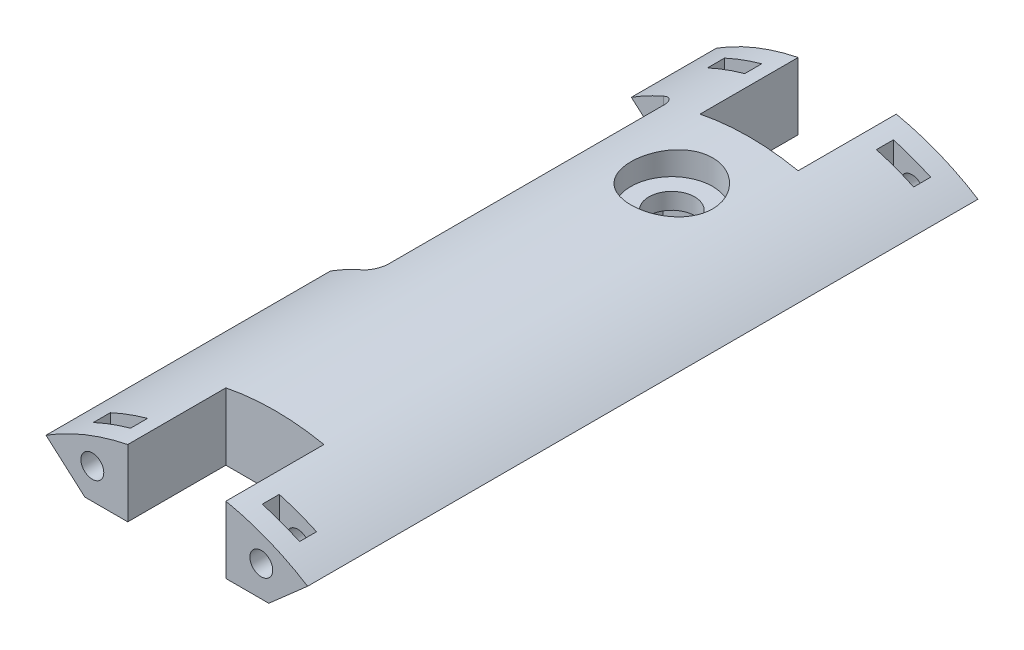
SolidWorks part; units mm, degrees
ref_plane "Plan de face" through (0, 0, 0) normal (0, 0, 1) x (1, 0, 0)
ref_plane "Plan de dessus" through (0, 0, 0) normal (0, 1, 0) x (1, 0, 0)
ref_plane "Plan de droite" through (0, 0, 0) normal (1, 0, 0) x (0, 0, -1)
sketch "Esquisse3" plane through (0, 0, 0) normal (0, 0, 1) x (1, 0, 0)
  line L0 (-14.0624, 26.5) -> (-20, 31.7214)
  line L1 (14.0624, 26.5) -> (20, 31.7214)
  line L2 (-14.0624, 26.5) -> (14.0624, 26.5)
  line L3 (-20, 31.7214) -> (20, 31.7214) construction
  line L4 (-20, 31.7214) -> (-20, 0) construction
  line L5 (-20, 0) -> (20, 0) construction
  line L6 (20, 31.7214) -> (20, 0) construction
  line L7 (8.9994, 41.4168) -> (9.1038, 41.3823)
  circle A0 centre (0, 0) radius 37.5 construction
  circle A1 centre (0, 0) radius 30 construction
  arc A2 (-20, 31.7214) -> (20, 31.7214) centre (0, 0) cw
  point P5 (0, 0)
  point P15 (0, 26.5)
  dimension "D1" = 75
  dimension "D2" = 60
  dimension "D4" = 26.5
  dimension "D3" = 40
extrude "Boss.-Extru.2" add sketch "Esquisse3" along normal blind 102.5 contours A2 L0 L2 L1 region at (0, 31.5038, 0)
sketch "Esquisse7" plane through (0, 0, 102.5) normal (0, 0, 1) x (1, 0, 0)
  line L0 (0, 33.75) -> (0, 0) construction
  line L1 (0, 0) -> (-12.9156, 31.1809) construction
  line L2 (0, 0) -> (12.9156, 31.1809) construction
  line L3 (-30, 0) -> (-37.5, 0) construction
  circle A0 centre (0, 0) radius 33.75 construction
  circle A2 centre (-12.9156, 31.1809) radius 1.75
  circle A3 centre (12.9156, 31.1809) radius 1.75
  circle A4 centre (0, 0) radius 37.5 construction
  circle A5 centre (0, 0) radius 30 construction
  arc A6 (20, 31.7214) -> (-20, 31.7214) centre (0, 0) ccw construction
  point P15 (-33.75, 0)
  dimension "D2" = 3.5
  dimension "D5" = 60
  dimension "D3" = 22.5
  dimension "D4" = 22.5
extrude "Enlèv. mat.-Extru.4" cut sketch "Esquisse7" against normal blind 12
sketch "Esquisse11" plane through (0, 0, 102.5) normal (0, 0, 1) x (1, 0, 0)
  line L0 (-12.9156, 31.1809) -> (-15.7656, 31.1809) construction
  line L1 (-15.7656, 31.1809) -> (-15.7656, 34.0249)
  line L2 (-15.7656, 31.1809) -> (-15.7656, 29.4264)
  line L3 (-15.7656, 29.4264) -> (-12.9156, 27.7809)
  line L4 (-12.9156, 27.7809) -> (-10.0656, 29.4264)
  line L5 (-10.0656, 29.4264) -> (-10.0656, 36.1239)
  line L6 (10.0656, 36.1239) -> (10.0656, 29.4264)
  line L7 (10.0656, 29.4264) -> (12.9156, 27.7809)
  line L8 (12.9156, 27.7809) -> (15.7656, 29.4264)
  line L9 (15.7656, 29.4264) -> (15.7656, 34.0249)
  line L10 (12.9156, 31.1809) -> (15.7656, 31.1809) construction
  line L11 (12.9156, 31.1809) -> (10.0656, 31.1809) construction
  line L12 (12.9156, 31.1809) -> (12.9156, 27.7809) construction
  line L13 (11.1341, 33.0694) -> (11.2201, 33.0694) construction
  arc A1 (20, 31.7214) -> (-20, 31.7214) centre (0, 0) ccw construction
  arc A2 (-15.7656, 34.0249) -> (-10.0656, 36.1239) centre (0, 0) cw
  arc A3 (10.0656, 36.1239) -> (15.7656, 34.0249) centre (0, 0) cw
  dimension "D1" = 5.7
  dimension "D2" = 120
  dimension "D3" = 3.4
  dimension "D4" = 5.7
  dimension "D5" = 3.4
  dimension "D6" = 120
extrude "Enlèv. mat.-Extru.5" cut sketch "Esquisse11" against normal blind 2.6 from offset 3 offset against normal yes
sketch "Esquisse12" plane through (0, 0, 0) normal (0, 0, -1) x (-1, 0, 0)
  line L0 (0, 0) -> (0, 33.75) construction
  line L1 (0, 0) -> (-12.9156, 31.1809) construction
  line L2 (0, 0) -> (12.9156, 31.1809) construction
  line L3 (-30, 0) -> (-37.5, 0) construction
  circle A0 centre (0, 0) radius 33.75 construction
  circle A1 centre (-12.9156, 31.1809) radius 1.75
  circle A2 centre (12.9156, 31.1809) radius 1.75
  circle A3 centre (0, 0) radius 30 construction
  circle A4 centre (0, 0) radius 37.5 construction
  arc A5 (20, 31.7214) -> (-20, 31.7214) centre (0, 0) ccw construction
  point P15 (-33.75, 0)
  dimension "D4" = 3.5
  dimension "D5" = 60
  dimension "D1" = 22.5
  dimension "D2" = 22.5
extrude "Enlèv. mat.-Extru.6" cut sketch "Esquisse12" against normal blind 12
sketch "Esquisse14" plane through (0, 0, 0) normal (0, 0, -1) x (-1, 0, 0)
  line L0 (-12.9156, 31.1809) -> (-15.7656, 31.1809) construction
  line L1 (-15.7656, 31.1809) -> (-15.7656, 34.0249)
  line L2 (-15.7656, 31.1809) -> (-15.7656, 29.4264)
  line L3 (-15.7656, 29.4264) -> (-12.9156, 27.7809)
  line L4 (-12.9156, 27.7809) -> (-10.0656, 29.4264)
  line L5 (-10.0656, 29.4264) -> (-10.0656, 36.1239)
  line L6 (10.0656, 36.1239) -> (10.0656, 29.4264)
  line L7 (10.0656, 29.4264) -> (12.9156, 27.7809)
  line L8 (12.9156, 27.7809) -> (15.7656, 29.4264)
  line L9 (15.7656, 29.4264) -> (15.7656, 34.0249)
  line L10 (11.1656, 31.1809) -> (14.6656, 31.1809) construction
  line L11 (-14.6656, 31.1809) -> (-11.1656, 31.1809) construction
  line L12 (-12.9156, 32.9309) -> (-12.9156, 29.4309) construction
  line L13 (12.9156, 32.9309) -> (12.9156, 29.4309) construction
  line L14 (12.9156, 31.1809) -> (10.0656, 31.1809) construction
  line L15 (12.9156, 31.1809) -> (15.7656, 31.1809) construction
  circle A1 centre (-12.9156, 31.1809) radius 1.75 construction
  arc A2 (-15.7656, 34.0249) -> (-10.0656, 36.1239) centre (0, 0) cw
  arc A3 (10.0656, 36.1239) -> (15.7656, 34.0249) centre (0, 0) cw
  arc A4 (20, 31.7214) -> (-20, 31.7214) centre (0, 0) ccw construction
  circle A5 centre (-12.9156, 31.1809) radius 1.75 construction
  circle A6 centre (12.9156, 31.1809) radius 1.75 construction
  circle A7 centre (12.9156, 31.1809) radius 1.75 construction
  point P31 (-12.9156, 31.1809)
  point P36 (12.9156, 31.1809)
  dimension "D1" = 5.7
  dimension "D6" = 3.4
  dimension "D2" = 120
  dimension "D3" = 3.4
  dimension "D4" = 5.7
  dimension "D5" = 120
extrude "Enlèv. mat.-Extru.7" cut sketch "Esquisse14" against normal blind 2.6 from offset 3 offset against normal yes
sketch "Esquisse18" plane through (0, 0, 0) normal (0, 0, -1) x (-1, 0, 0)
  line L0 (14.0624, 26.5) -> (-14.0624, 26.5) construction
  line L1 (-7.15, 26.5) -> (7.15, 26.5)
  line L2 (-7.15, 26.5) -> (-7.15, 31.2)
  line L3 (-7.15, 31.2) -> (7.15, 31.2)
  line L4 (7.15, 26.5) -> (7.15, 31.2)
  point P6 (0, 31.2)
  dimension "D1" = 31.2
  dimension "D2" = 14.3
extrude "Enlèv. mat.-Extru.11" cut sketch "Esquisse18" against normal blind 11.74 from offset 21 offset against normal yes
sketch "Esquisse19" plane through (0, 31.2, 0) normal (0, -1, 0) x (-1, 0, 0)
  circle A0 centre (0, -26.82) radius 3.5
  dimension "D1" = 7
extrude "Enlèv. mat.-Extru.12" cut sketch "Esquisse19" against normal through all
sketch "Esquisse20" plane through (0, 31.2, 0) normal (0, -1, 0) x (-1, 0, 0)
  circle A0 centre (0, -26.82) radius 6.25
  dimension "D1" = 12.5
extrude "Enlèv. mat.-Extru.13" cut sketch "Esquisse20" against normal through all from offset 2.5 offset against normal yes
sketch "Esquisse21" plane through (0, 26.5, 0) normal (0, -1, 0) x (1, 0, 0)
  line L0 (-14.0624, 102.5) -> (14.0624, 102.5) construction
  line L1 (-7.5, 102.5) -> (7.5, 102.5)
  line L2 (-7.5, 102.5) -> (-7.5, 87.5)
  line L3 (-7.5, 87.5) -> (7.5, 87.5)
  line L4 (7.5, 102.5) -> (7.5, 87.5)
  line L5 (-14.0624, 0) -> (14.0624, 0) construction
  line L6 (-7.5, 0) -> (7.5, 0)
  line L7 (-7.5, 0) -> (-7.5, 15)
  line L8 (-7.5, 15) -> (7.5, 15)
  line L9 (7.5, 0) -> (7.5, 15)
  point P12 (0, 87.5)
  point P13 (0, 15)
  dimension "D1" = 15
  dimension "D2" = 15
extrude "Enlèv. mat.-Extru.14" cut sketch "Esquisse21" against normal through all
sketch "Esquisse22" plane through (0, 26.5, 0) normal (0, -1, 0) x (-1, 0, 0)
  line L1 (-8.325, -90.25) -> (-10.575, -90.25)
  line L2 (-8.325, -90.25) -> (-8.325, -74.75)
  line L3 (-8.325, -74.75) -> (-10.575, -74.75)
  line L4 (-10.575, -90.25) -> (-10.575, -74.75)
  line L7 (-7.5, -102.5) -> (-14.0624, -102.5) construction
  line L8 (7.5, -87.5) -> (-7.5, -87.5) construction
  point P6 (-10.575, -82.5)
  point P9 (0, -87.5)
  point P10 (-9.45, -74.75)
  dimension "D1" = 9.45
  dimension "D2" = 2.25
  dimension "D3" = 15.5
  dimension "D4" = 20
extrude "Enlèv. mat.-Extru.15" cut sketch "Esquisse22" against normal blind 9.125
chamfer "Chanfrein1" distance 9.125 angle 45 2 edges at (9.45, 35.625, 90.25) (9.45, 35.625, 74.75)
fillet "Congé1" radius 4 1 edges at (9.45, 34.25, 82.5)
sketch "Esquisse23" plane through (0, 26.5, 0) normal (0, -1, 0) x (-1, 0, 0)
  line L0 (20, -59) -> (13.0624, -59)
  line L1 (20, -59) -> (20, -13)
  line L2 (13.0624, -59) -> (13.0624, -13)
  line L3 (20, -13) -> (13.0624, -13)
  line L4 (14.0624, 0) -> (7.5, 0) construction
  line L5 (14.0624, -102.5) -> (14.0624, 0) construction
  line L6 (20, -102.5) -> (20, 0) construction
  dimension "D2" = 46
  dimension "D3" = 13
  dimension "D4" = 1
extrude "Enlèv. mat.-Extru.16" cut sketch "Esquisse23" against normal through all
fillet "Congé2" radius 2 2 edges at (-13.0624, 30.8257, 59) (-13.0624, 30.8257, 13)
